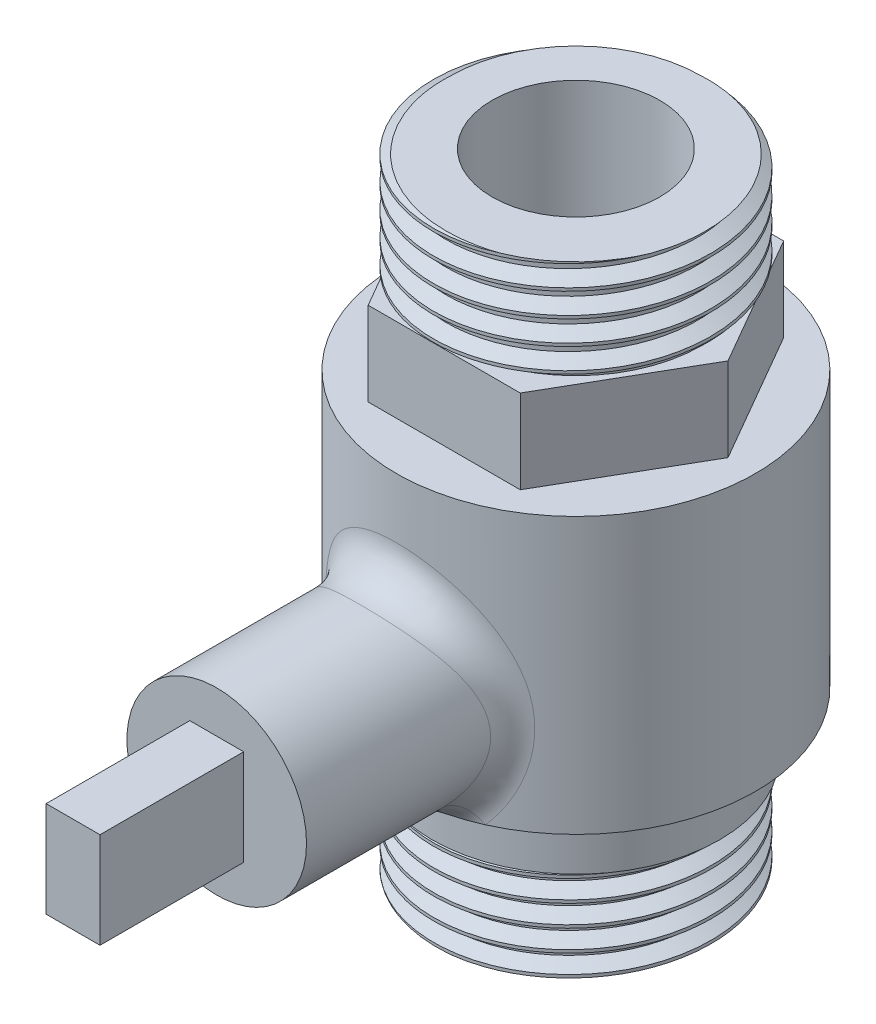
SolidWorks part; units mm, degrees
ref_plane "Plan de face" through (0, 0, 0) normal (0, 0, 1) x (1, 0, 0)
ref_plane "Plan de dessus" through (0, 0, 0) normal (0, 1, 0) x (1, 0, 0)
ref_plane "Plan de droite" through (0, 0, 0) normal (1, 0, 0) x (0, 0, -1)
sketch "Esquisse1" plane through (0, 0, 0) normal (0, 0, 1) x (1, 0, 0)
  line L0 (0, 0) -> (-10.5, 0)
  line L1 (-10.5, 0) -> (-10.5, 8)
  line L2 (-10.5, 8) -> (-12, 8)
  line L3 (-12, 8) -> (-12, 13)
  line L4 (-12, 13) -> (-15, 13)
  line L5 (-15, 13) -> (-15, 36)
  line L6 (-15, 36) -> (-10.5, 36)
  line L9 (-10.5, 36) -> (-10.5, 52)
  line L10 (-10.5, 52) -> (0, 52)
  line L11 (0, 52) -> (0, 0)
  point P3 (0, 0)
  dimension "D1" = 10.5
  dimension "D2" = 8
  dimension "D3" = 12
  dimension "D4" = 5
  dimension "D5" = 15
  dimension "D6" = 23
  dimension "D7" = 10.5
  dimension "D8" = 16
  dimension "D9" = 52
revolve "Révolution1" add sketch "Esquisse1" angle 360 about L11
sketch "Esquisse2" plane through (0, 36, 0) normal (0, 1, 0) x (1, 0, 0)
  line L1 (-6.3509, -11) -> (6.3509, -11)
  line L2 (6.3509, -11) -> (12.7017, 0)
  line L3 (12.7017, 0) -> (6.3509, 11)
  line L4 (6.3509, 11) -> (-6.3509, 11)
  line L5 (-6.3509, 11) -> (-12.7017, 0)
  line L6 (-12.7017, 0) -> (-6.3509, -11)
  circle A0 centre (0, 0) radius 11 construction
  dimension "D1" = 22
extrude "Boss.-Extru.1" add sketch "Esquisse2" along normal blind 7
sketch "Esquisse3" plane through (0, 0, 0) normal (0, 0, 1) x (1, 0, 0)
  line L4 (-12, 13) -> (12, 13) construction
  circle A0 centre (0, 20.5) radius 7.5
  point P2 (-15.9463, 20.5)
  point P3 (0, 0)
  point P4 (0, 0)
  dimension "D1" = 15
extrude "Boss.-Extru.2" add sketch "Esquisse3" along normal blind 30
sketch "Esquisse4" plane through (0, 0, 30) normal (0, 0, 1) x (1, 0, 0)
  line L1 (-2.25, 24.5) -> (2.25, 24.5)
  line L2 (-2.25, 24.5) -> (-2.25, 16.5)
  line L3 (-2.25, 16.5) -> (2.25, 16.5)
  line L4 (2.25, 24.5) -> (2.25, 16.5)
  circle A2 centre (0, 20.5) radius 10.7701 construction
  circle A3 centre (0, 20.5) radius 7.5 construction
  point P4 (0, 24.5)
  point P10 (0, 0)
  point P11 (2.25, 20.5)
  dimension "D1" = 4.5
  dimension "D2" = 8
extrude "Boss.-Extru.3" add sketch "Esquisse4" along normal blind 12
fillet "Congé1" radius 3 1 edges at (0.7568, 27.9617, 14.9809)
thread "Filetage1" pitch 2 method extrude trim with start face yes trim with end face yes profile "Profil de filetage1" start angle 0, offset 2, length 0, pitch 1.8, diameter 21
ref_plane "Plan1" through (10.5, -2, 0) normal (0, 0, 1) x (1, 0, 0)
sketch "Profil de filetage1" plane through (10.5, -2, 0) normal (0, 0, 1) x (1, 0, 0)
  line L0 (0, 0) -> (0, 2) construction
  line L1 (0, 0) -> (1.0825, 0.625)
  line L2 (1.0825, 0.625) -> (1.0825, 0.875)
  line L3 (1.0825, 0.875) -> (0, 1.5)
  line L4 (1.0825, 0.75) -> (0, 0.75) construction
  line L11 (0, 0) -> (0, 1.5)
  point P2 (0, 0)
  dimension "Pitch" = 2
  dimension "Profile_Angle" = 60
  dimension "Profile_Land" = 0.25
  dimension "Profile_Height" = 1.0825
thread "Filetage2" pitch 2 method extrude trim with start face yes trim with end face yes profile "Profil de filetage2" start angle 0, offset 2, length 0, pitch 2, diameter 21
ref_plane "Plan2" through (-10.5, 54, 0) normal (0, 0, 1) x (-1, 0, 0)
sketch "Profil de filetage2" plane through (-10.5, 54, 0) normal (0, 0, 1) x (-1, 0, 0)
  line L0 (0, 0) -> (0, 2) construction
  line L1 (0, 0) -> (1.0825, 0.625)
  line L2 (1.0825, 0.625) -> (1.0825, 0.875)
  line L3 (1.0825, 0.875) -> (0, 1.5)
  line L4 (1.0825, 0.75) -> (0, 0.75) construction
  line L11 (0, 0) -> (0, 1.5)
  point P2 (0, 0)
  dimension "Pitch" = 2
  dimension "Profile_Angle" = 60
  dimension "Profile_Land" = 0.25
  dimension "Profile_Height" = 1.0825
sketch "Esquisse10" plane through (0, 0, 0) normal (0, -1, 0) x (1, 0, 0)
  circle A0 centre (0, 0) radius 7
  dimension "D1" = 14
extrude "Enlèv. mat.-Extru.1" cut sketch "Esquisse10" against normal through all
